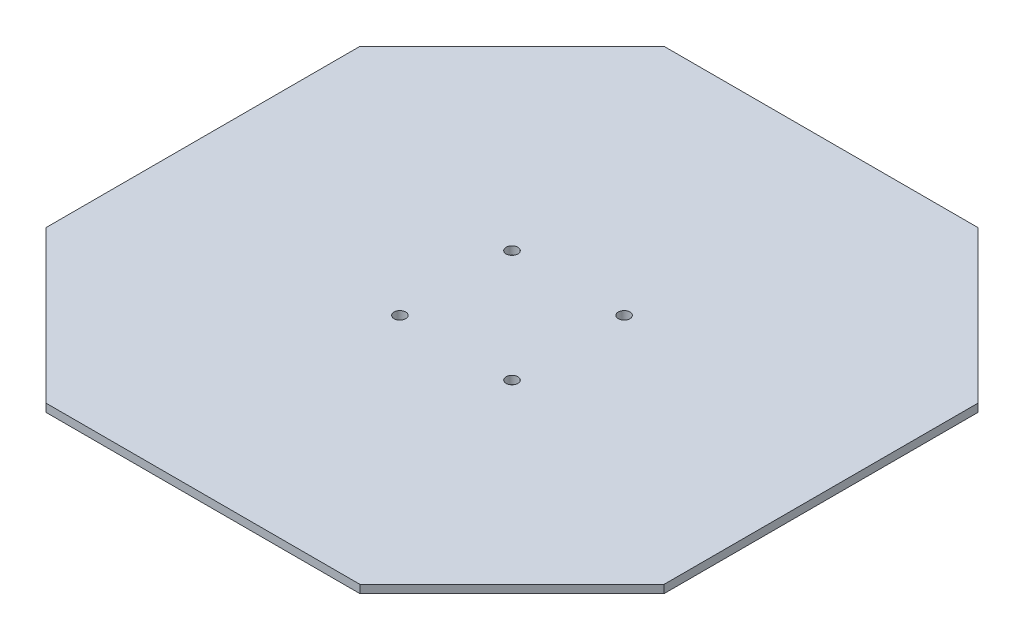
SolidWorks part; units mm, degrees
ref_plane "Front Plane" through (0, 0, 0) normal (0, 0, 1) x (1, 0, 0)
ref_plane "Top Plane" through (0, 0, 0) normal (0, 1, 0) x (1, 0, 0)
ref_plane "Right Plane" through (0, 0, 0) normal (1, 0, 0) x (0, 0, -1)
sketch "Sketch1" plane through (0, 0, 0) normal (0, 1, 0) x (1, 0, 0)
  line L1 (0, 0) -> (230, 0)
  line L2 (0, 0) -> (0, 230)
  line L3 (0, 230) -> (230, 230)
  line L4 (230, 0) -> (230, 230)
  dimension "D1" = 230
  dimension "D2" = 230
extrude "Boss-Extrude1" add sketch "Sketch1" along normal blind 3
fillet "Chamfer2" radius 56.5685 1 edges at (0, 1.5, 0) type face fillet profile chamfer first side face at (115, 1.5, 0) second side face at (0, 1.5, -115)
fillet "Chamfer3" radius 56.5685 1 edges at (0, 1.5, -230) type face fillet profile chamfer first side face at (0, 1.5, -143.2843) second side face at (115, 1.5, -230)
fillet "Chamfer4" radius 56.5685 1 edges at (230, 1.5, -230) type face fillet profile chamfer first side face at (143.2842, 1.5, -230) second side face at (230, 1.5, -115)
fillet "Chamfer5" radius 56.5685 1 edges at (230, 1.5, 0) type face fillet profile chamfer first side face at (230, 1.5, -86.7158) second side face at (143.2843, 1.5, 0)
hole_wizard "11/64 (0.17188) Diameter Hole1" positions "Sketch4" profile "Sketch3" hole size "11/64" standard "ANSI Inch" end condition up to next
sketch "Sketch4" plane through (0, 3, 0) normal (0, 1, 0) x (1, 0, 0)
  point P0 (94.1403, 135.8597)
  point P3 (135.8597, 135.8597)
  point P6 (135.8597, 94.1403)
  point P9 (94.1403, 94.1403)
sketch "Sketch3" plane through (94.1403, 3, -135.8597) normal (1, 0, 0) x (0, 0, 1)
  line L0 (0, 0) -> (0, 3)
  line L1 (0, 3) -> (2.1829, 3)
  line L2 (2.1829, 3) -> (2.1829, 0)
  line L5 (2.1829, 0) -> (0, 0)
  line L11 (0, -6.35) -> (0, 107.95) construction
  dimension "Thru Hole Dia." = 4.3658
  dimension "Thru Hole Depth" = 3
